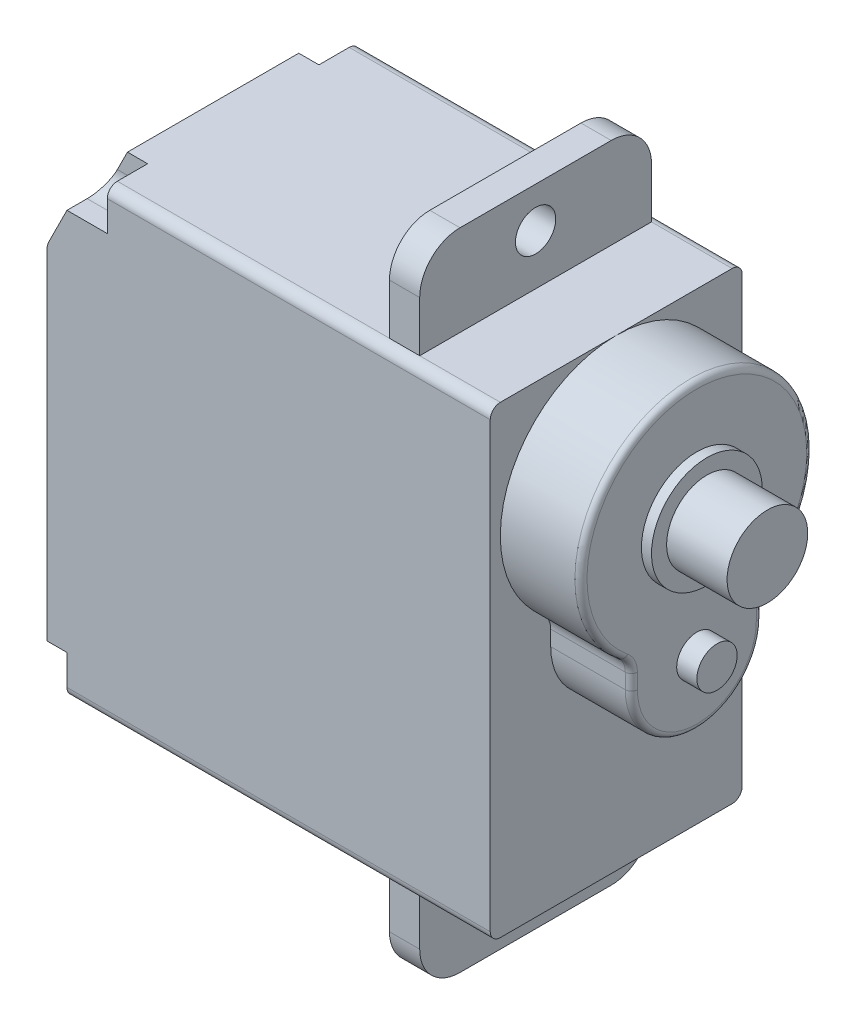
SolidWorks part; units mm, degrees
ref_plane "前视基准面" through (0, 0, 0) normal (0, 0, 1) x (1, 0, 0)
ref_plane "上视基准面" through (0, 0, 0) normal (0, 1, 0) x (1, 0, 0)
ref_plane "右视基准面" through (0, 0, 0) normal (1, 0, 0) x (0, 0, -1)
sketch "Sketch1" plane through (0, 0, 0) normal (0, 0, 1) x (1, 0, 0)
  line L1 (-11, 11.5) -> (11, 11.5)
  line L2 (-11, 11.5) -> (-11, -11.5)
  line L3 (-11, -11.5) -> (11, -11.5)
  line L4 (11, 11.5) -> (11, -11.5)
  line L5 (-11, 11.5) -> (11, -11.5) construction
  line L6 (-11, -11.5) -> (11, 11.5) construction
  point P0 (0, 0)
  dimension "D1" = 22
  dimension "D2" = 23
extrude "Extrude1" add sketch "Sketch1" along normal mid plane 12.5
sketch "Sketch2" plane through (11, 0, 0) normal (1, 0, 0) x (0, 0, -1)
  line L0 (-6.25, 11.5) -> (6.25, 11.5) construction
  line L2 (-3.25, -0.25) -> (-3.25, 1.0066)
  line L3 (0, 5.2955) -> (0, -4.8164) construction
  line L4 (3.25, -0.25) -> (3.25, 1.0066)
  arc A0 (3.25, 1.0066) -> (-3.25, 1.0066) centre (0, 5.75) ccw
  arc A1 (-3.25, -0.25) -> (3.25, -0.25) centre (0, -0.25) ccw
  dimension "D1" = 11.5
  dimension "D2" = 6.5
  dimension "D3" = 15
extrude "Extrude2" add sketch "Sketch2" along normal blind 4
sketch "Sketch3" plane through (15, 0, 0) normal (1, 0, 0) x (0, 0, -1)
  circle A0 centre (0, 5.75) radius 2
  dimension "D1" = 4
extrude "Extrude3" add sketch "Sketch3" along normal blind 3.5
sketch "Sketch4" plane through (0, 0, 6.25) normal (0, 0, 1) x (1, 0, 0)
  line L0 (-9, 11.5) -> (-11, 11.5)
  line L1 (11, 11.5) -> (-11, 11.5) construction
  line L2 (-11, 11.5) -> (-11, 7.5)
  line L3 (-11, 11.5) -> (-11, -11.5) construction
  line L4 (-11, 7.5) -> (-9, 11.5)
  dimension "D1" = 2
  dimension "D2" = 4
extrude "Extrude4" cut sketch "Sketch4" against normal through all
fillet "Fillet1" radius 1 3 edges at (13, 1.0066, -3.25) (13, 1.0066, 3.25) (-11, 7.5, 0)
sketch "Sketch5" plane through (15, 0, 0) normal (1, 0, 0) x (0, 0, -1)
  circle A0 centre (0, -0.25) radius 1
  dimension "D1" = 2
extrude "Extrude5" add sketch "Sketch5" along normal blind 1
sketch "Sketch6" plane through (15, 0, 0) normal (1, 0, 0) x (0, 0, -1)
  circle A0 centre (0, 5.75) radius 2.75
  dimension "D1" = 5.5
extrude "Extrude6" add sketch "Sketch6" along normal blind 0.5
sketch "Sketch7" plane through (-11, 0, 0) normal (-1, 0, 0) x (0, 0, 1)
  line L0 (-6.25, 7.2639) -> (-6.25, -11.5) construction
  line L1 (6.25, -11.5) -> (-6.25, -11.5) construction
  line L2 (-5.25, -9.5) -> (-6.25, -9.5)
  line L3 (-4.25, -10.5) -> (-4.25, -11.5)
  line L4 (-6.25, -9.5) -> (-6.25, -11.5)
  line L5 (-6.25, -11.5) -> (-4.25, -11.5)
  line L6 (0, 5.9798) -> (0, -14.4689) construction
  line L7 (6.25, -11.5) -> (4.25, -11.5)
  line L8 (6.25, -9.5) -> (6.25, -11.5)
  line L9 (4.25, -10.5) -> (4.25, -11.5)
  line L10 (5.25, -9.5) -> (6.25, -9.5)
  line L11 (-11.5064, 0) -> (8.4476, 0) construction
  line L12 (5.25, 9.5) -> (6.25, 9.5)
  line L13 (4.25, 10.5) -> (4.25, 11.5)
  line L14 (6.25, 9.5) -> (6.25, 11.5)
  line L15 (6.25, 11.5) -> (4.25, 11.5)
  line L16 (-6.25, 11.5) -> (-4.25, 11.5)
  line L17 (-6.25, 9.5) -> (-6.25, 11.5)
  line L18 (-4.25, 10.5) -> (-4.25, 11.5)
  line L19 (-5.25, 9.5) -> (-6.25, 9.5)
  arc A0 (-4.25, -10.5) -> (-5.25, -9.5) centre (-5.25, -10.5) ccw
  arc A1 (4.25, -10.5) -> (5.25, -9.5) centre (5.25, -10.5) cw
  arc A2 (4.25, 10.5) -> (5.25, 9.5) centre (5.25, 10.5) ccw
  arc A3 (-4.25, 10.5) -> (-5.25, 9.5) centre (-5.25, 10.5) cw
  dimension "D1" = 2
extrude "Extrude7" cut sketch "Sketch7" against normal blind 1
extrude "Extrude8" cut sketch "Sketch" against normal blind 1 and the other way through all from vertex contours A3 L18 L16 L17 L19 | L13 A2 L12 L14 L15 region at (-11, 10.544, 5.294) region at (-11, 10.544, -5.294) starting at point (-9, 11.5, -6.25)
sketch "Sketch" plane through (-11, 0, 0) normal (-1, 0, 0) x (0, 0, 1) same geometry as "Sketch7"
sketch "Sketch8" plane through (0, 0, 0) normal (0, 0, 1) x (1, 0, 0)
  line L1 (5.5, 11.5) -> (7, 11.5)
  line L2 (5.5, 11.5) -> (5.5, 16)
  line L3 (5.5, 16) -> (7, 16)
  line L4 (7, 11.5) -> (7, 16)
  line L5 (11, -11.5) -> (11, 11.5) construction
  line L6 (-14.9129, 0) -> (20.3595, 0) construction
  line L7 (7, -11.5) -> (7, -16)
  line L8 (5.5, -16) -> (7, -16)
  line L9 (5.5, -11.5) -> (5.5, -16)
  line L10 (5.5, -11.5) -> (7, -11.5)
  line L11 (11, 11.5) -> (-8, 11.5) construction
  dimension "D1" = 5.5
  dimension "D2" = 1.5
  dimension "D3" = 32
extrude "Extrude9" add sketch "Sketch8" along normal mid plane 11.5
fillet "Fillet3" radius 0.3 6 edges at (15, 0.9363, -3.3473) (15, 0.128, -3.25) (15, -3.5, 0) (15, 0.128, 3.25) (15, 0.9363, 3.3473) (15, 11.5, 0)
fillet "Fillet4" radius 0.5 4 edges at (0.5, -11.5, -6.25) (0.5, -11.5, 6.25) (1.5, 11.5, -6.25) (1.5, 11.5, 6.25)
fillet "Fillet5" radius 2 4 edges at (6.25, 16, 5.75) (6.25, 16, -5.75) (6.25, -16, 5.75) (6.25, -16, -5.75)
sketch "Sketch9" plane through (7, 0, 0) normal (1, 0, 0) x (0, 0, -1)
  line L0 (0, 17.3642) -> (0, -17.7317) construction
  line L1 (-9.4814, 0) -> (12.4949, 0) construction
  line L2 (-3.75, 16) -> (3.75, 16) construction
  circle A0 centre (0, 14) radius 1
  dimension "D1" = 2
  dimension "D2" = 2
extrude "Extrude10" cut sketch "Sketch9" against normal blind 11.5 contours A0
mirror "Mirror1" about plane through (0, 0, 0) normal (0, 1, 0) of "Extrude10"
sketch "Sketch10" plane through (5.5, 0, 0) normal (-1, 0, 0) x (0, 0, 1)
  line L9 (5.75, 11.5) -> (-5.75, 11.5) construction
  line L10 (4.95, 11.5) -> (0, 11.5)
  line L11 (2.5, 14) -> (2.5, 15.2)
  line L12 (4.95, 14) -> (4.95, 11.5)
  line L13 (-4.95, 11.5) -> (-4.95, 14)
  line L14 (-3.75, 15.2) -> (3.75, 15.2)
  line L15 (4.95, 14) -> (4.95, 11.5)
  line L16 (-4.95, 11.5) -> (-4.95, 14)
  line L17 (-3.75, 15.2) -> (-2.5, 15.2)
  line L18 (-2.5, 14) -> (-2.5, 15.2)
  line L19 (2.5, 15.2) -> (3.75, 15.2)
  line L20 (0, 11.5) -> (-4.95, 11.5)
  arc A6 (-2.5, 14) -> (0, 11.5) centre (0, 14) ccw
  arc A7 (0, 11.5) -> (2.5, 14) centre (0, 14) ccw
  arc A8 (4.95, 14) -> (3.75, 15.2) centre (3.75, 14) ccw
  arc A9 (-3.75, 15.2) -> (-4.95, 14) centre (-3.75, 14) ccw
  arc A10 (4.95, 14) -> (3.75, 15.2) centre (3.75, 14) ccw
  arc A11 (-3.75, 15.2) -> (-4.95, 14) centre (-3.75, 14) ccw
  dimension "D2" = 5
  dimension "D1" = 0.8
equation "\"23。5\"=23"
